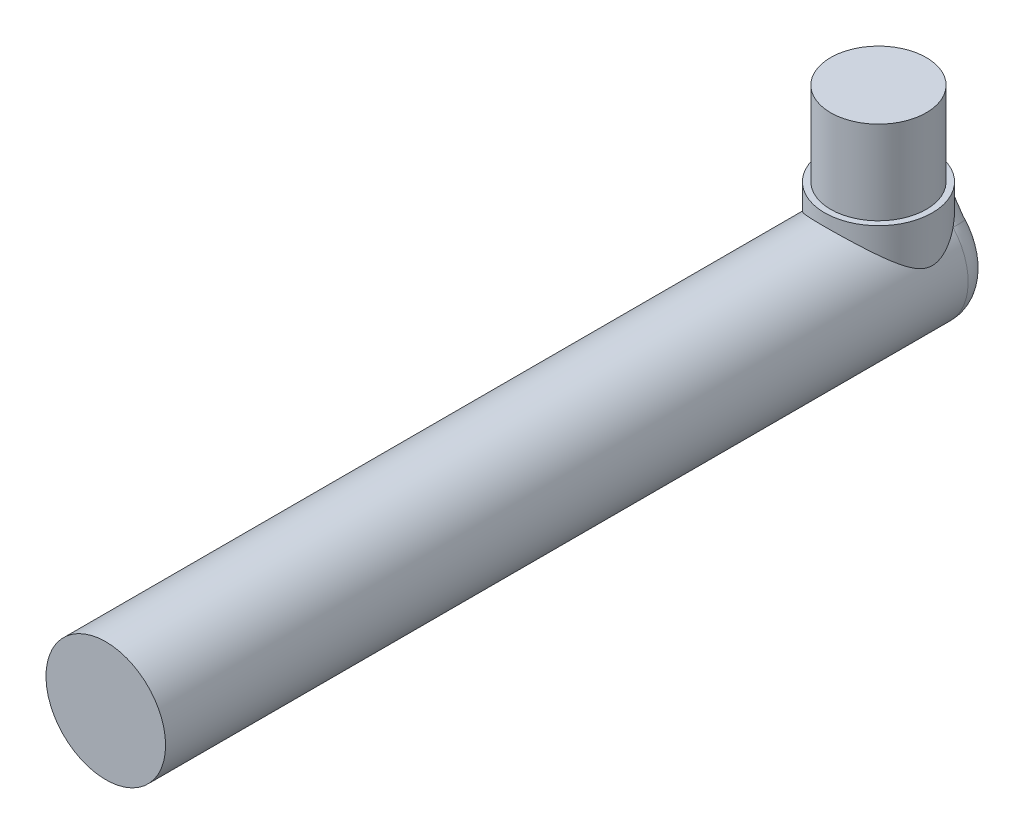
SolidWorks part; units mm, degrees
ref_plane "Front Plane" through (0, 0, 0) normal (0, 0, 1) x (1, 0, 0)
ref_plane "Top Plane" through (0, 0, 0) normal (0, 1, 0) x (1, 0, 0)
ref_plane "Right Plane" through (0, 0, 0) normal (1, 0, 0) x (0, 0, -1)
sketch "Sketch1" plane through (0, 0, 0) normal (0, 0, 1) x (1, 0, 0)
  circle A0 centre (0, 0) radius 5
  dimension "D1" = 10
extrude "Boss-Extrude1" add sketch "Sketch1" along normal blind 70
sketch "Sketch2" plane through (0, 0, 0) normal (0, 1, 0) x (1, 0, 0)
  circle A0 centre (0, -5.3867) radius 4.5
  dimension "D1" = 9
extrude "Boss-Extrude2" add sketch "Sketch2" along normal blind 6
sketch "Sketch3" plane through (0, 0, 0) normal (0, 0, -1) x (-1, 0, 0)
  circle A0 centre (0, 0) radius 5
extrude "Cut-Extrude2" cut sketch "Sketch3" against normal blind 0.8867
fillet "Fillet1" radius 2 1 edges at (-5, 0, 0.8867)
sketch "Sketch4" plane through (0, 6, 0) normal (0, 1, 0) x (1, 0, 0)
  circle A0 centre (0, -5.3867) radius 4
  dimension "D1" = 8
extrude "Boss-Extrude3" add sketch "Sketch4" along normal blind 7
